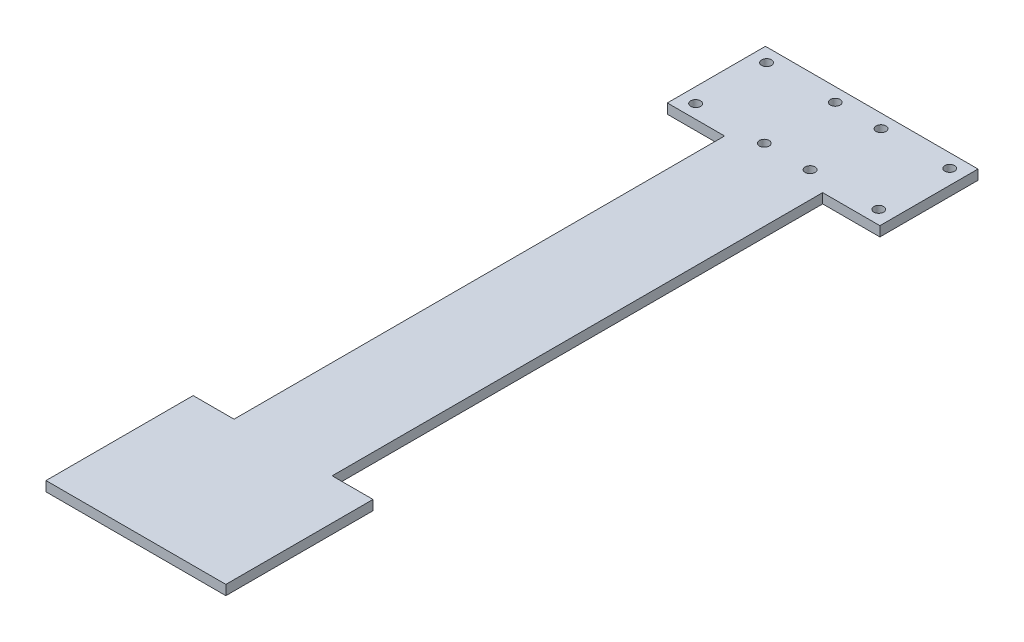
SolidWorks part; units mm, degrees
ref_plane "Front Plane" through (0, 0, 0) normal (0, 0, 1) x (1, 0, 0)
ref_plane "Top Plane" through (0, 0, 0) normal (0, 1, 0) x (1, 0, 0)
ref_plane "Right Plane" through (0, 0, 0) normal (1, 0, 0) x (0, 0, -1)
sketch "Sketch1" plane through (0, 0, 0) normal (0, 1, 0) x (1, 0, 0)
  line L0 (0, 0) -> (0, 225) construction
  line L1 (32.5, 225) -> (-32.5, 225)
  line L2 (-32.5, 225) -> (-32.5, 195)
  line L3 (-32.5, 195) -> (-15, 195)
  line L4 (-15, 195) -> (-15, 45)
  line L5 (-15, 45) -> (-27.5, 45)
  line L6 (-27.5, 45) -> (-27.5, 0)
  line L7 (-27.5, 0) -> (27.5, 0)
  line L8 (27.5, 45) -> (27.5, 0)
  line L9 (15, 45) -> (27.5, 45)
  line L10 (15, 195) -> (15, 45)
  line L11 (32.5, 195) -> (15, 195)
  line L12 (32.5, 225) -> (32.5, 195)
  dimension "D1" = 65
  dimension "D2" = 30
  dimension "D3" = 55
  dimension "D4" = 30
  dimension "D5" = 45
  dimension "D6" = 150
extrude "Boss-Extrude1" add sketch "Sketch1" along normal blind 3
sketch "Sketch2" plane through (0, 3, 0) normal (0, 1, 0) x (1, 0, 0)
  line L0 (0, 225) -> (0, 0) construction
  line L1 (32.5, 225) -> (-32.5, 225) construction
  line L2 (-28, 225) -> (-28, 199.15) construction
  line L3 (-7, 225) -> (-7, 199.15) construction
  line L4 (-28, 220.85) -> (-7, 220.85) construction
  line L5 (-17.5, 220.85) -> (-17.5, 130.7949) construction
  line L6 (-28, 210) -> (-7, 210) construction
  line L7 (-32.5, 210) -> (32.5, 210) construction
  line L8 (-32.5, 225) -> (-32.5, 195) construction
  line L9 (32.5, 195) -> (32.5, 225) construction
  circle A0 centre (-28, 220.85) radius 1.5
  circle A1 centre (-7, 220.85) radius 1.5
  circle A2 centre (-28, 199.15) radius 1.5
  circle A3 centre (-7, 199.15) radius 1.5
  dimension "D3" = 21.7
  dimension "D4" = 3
  dimension "D1" = 21
  dimension "D2" = 17.5
extrude "Cut-Extrude1" cut sketch "Sketch2" against normal through all both and the other way through all
mirror "Mirror1" about plane through (0, 0, 0) normal (1, 0, 0) of "Cut-Extrude1"
